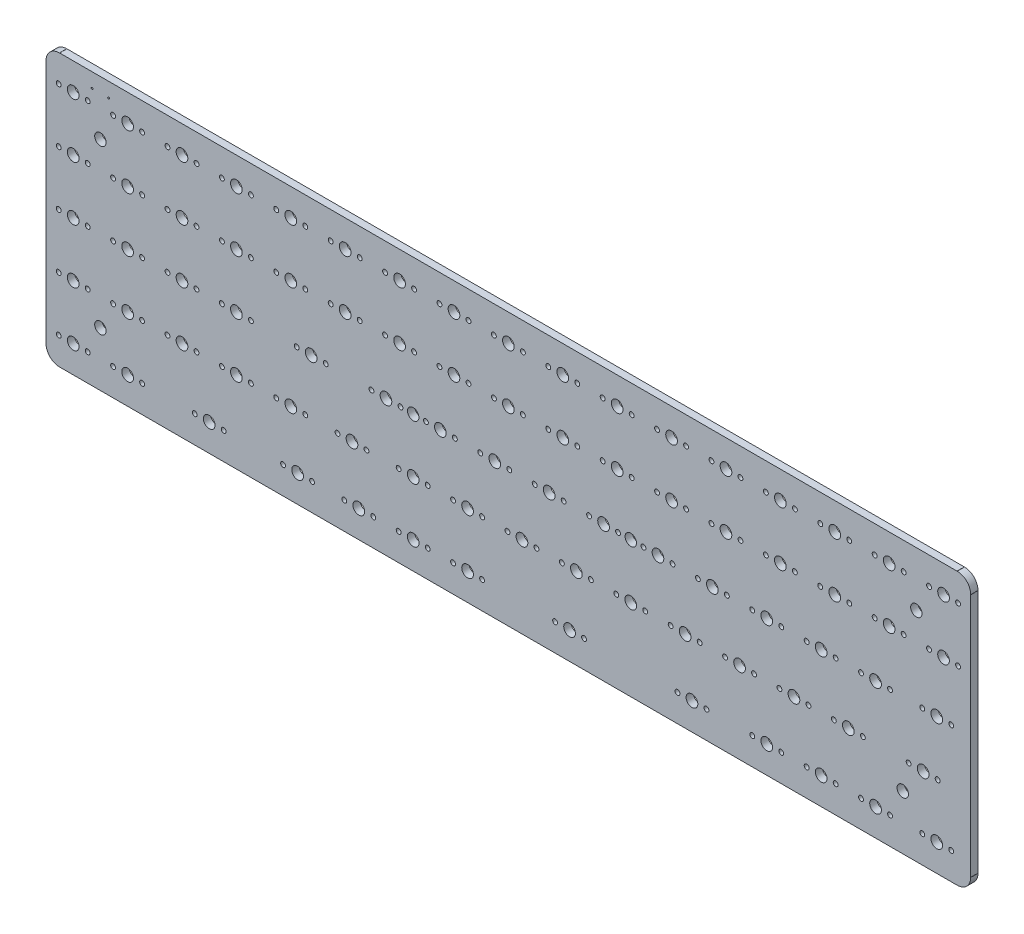
SolidWorks part; units mm, degrees
ref_plane "Front" through (0, 0, 0) normal (0, 0, 1) x (1, 0, 0)
ref_plane "Top" through (0, 0, 0) normal (0, 1, 0) x (1, 0, 0)
ref_plane "Right" through (0, 0, 0) normal (1, 0, 0) x (0, 0, -1)
sketch "Sketch2" plane through (0, 0, 0) normal (0, 0, 1) x (1, 0, 0)
  line L0 (314.325, -4.7625) -> (314.325, 80.9625)
  line L1 (309.5625, 85.725) -> (-4.7625, 85.725)
  line L2 (-9.525, 80.9625) -> (-9.525, -4.7625)
  line L3 (-4.7625, -9.525) -> (309.5625, -9.525)
  arc A0 (314.3631, 80.9625) -> (314.2869, 80.9625) centre (314.325, 80.9625) ccw
  arc A1 (314.2869, -4.7625) -> (314.3631, -4.7625) centre (314.325, -4.7625) ccw
  arc A2 (314.325, 80.9625) -> (309.5625, 85.725) centre (309.5624, 80.9624) ccw
  arc A3 (314.2869, 80.9625) -> (314.3631, 80.9625) centre (314.325, 80.9625) ccw
  arc A4 (309.5625, 85.7631) -> (309.5625, 85.6869) centre (309.5625, 85.725) ccw
  arc A5 (-4.7625, 85.7631) -> (-4.7625, 85.6869) centre (-4.7625, 85.725) ccw
  arc A6 (309.5625, 85.6869) -> (309.5625, 85.7631) centre (309.5625, 85.725) ccw
  arc A7 (-4.7625, 85.725) -> (-9.525, 80.9625) centre (-4.7624, 80.9624) ccw
  arc A8 (-4.7625, 85.6869) -> (-4.7625, 85.7631) centre (-4.7625, 85.725) ccw
  arc A9 (-9.5631, 80.9625) -> (-9.4869, 80.9625) centre (-9.525, 80.9625) ccw
  arc A10 (-9.5631, -4.7625) -> (-9.4869, -4.7625) centre (-9.525, -4.7625) ccw
  arc A11 (-9.4869, 80.9625) -> (-9.5631, 80.9625) centre (-9.525, 80.9625) ccw
  arc A12 (-9.525, -4.7625) -> (-4.7625, -9.525) centre (-4.7624, -4.7624) ccw
  arc A13 (-9.4869, -4.7625) -> (-9.5631, -4.7625) centre (-9.525, -4.7625) ccw
  arc A14 (-4.7625, -9.5631) -> (-4.7625, -9.4869) centre (-4.7625, -9.525) ccw
  arc A15 (309.5625, -9.5631) -> (309.5625, -9.4869) centre (309.5625, -9.525) ccw
  arc A16 (-4.7625, -9.4869) -> (-4.7625, -9.5631) centre (-4.7625, -9.525) ccw
  arc A17 (309.5625, -9.525) -> (314.325, -4.7625) centre (309.5624, -4.7624) ccw
  arc A18 (309.5625, -9.4869) -> (309.5625, -9.5631) centre (309.5625, -9.525) ccw
  arc A19 (314.3631, -4.7625) -> (314.2869, -4.7625) centre (314.325, -4.7625) ccw
  circle A20 centre (9.525, 66.675) radius 2
  circle A21 centre (9.525, 9.525) radius 2
  circle A22 centre (295.275, 66.675) radius 2
  circle A23 centre (290.5125, 9.525) radius 2
  circle A24 centre (119.0625, 38.1) radius 2
  circle A25 centre (195.2625, 38.1) radius 2
  circle A26 centre (304.8, 76.2) radius 2.0447
  circle A27 centre (299.72, 76.2) radius 0.8534
  circle A28 centre (309.88, 76.2) radius 0.8534
  circle A29 centre (285.75, 76.2) radius 2.0447
  circle A30 centre (280.67, 76.2) radius 0.8534
  circle A31 centre (290.83, 76.2) radius 0.8534
  circle A32 centre (266.7, 76.2) radius 2.0447
  circle A33 centre (261.62, 76.2) radius 0.8534
  circle A34 centre (271.78, 76.2) radius 0.8534
  circle A35 centre (247.65, 76.2) radius 2.0447
  circle A36 centre (242.57, 76.2) radius 0.8534
  circle A37 centre (252.73, 76.2) radius 0.8534
  circle A38 centre (228.6, 76.2) radius 2.0447
  circle A39 centre (223.52, 76.2) radius 0.8534
  circle A40 centre (233.68, 76.2) radius 0.8534
  circle A41 centre (209.55, 76.2) radius 2.0447
  circle A42 centre (204.47, 76.2) radius 0.8534
  circle A43 centre (214.63, 76.2) radius 0.8534
  circle A44 centre (190.5, 76.2) radius 2.0447
  circle A45 centre (185.42, 76.2) radius 0.8534
  circle A46 centre (195.58, 76.2) radius 0.8534
  circle A47 centre (171.45, 76.2) radius 2.0447
  circle A48 centre (166.37, 76.2) radius 0.8534
  circle A49 centre (176.53, 76.2) radius 0.8534
  circle A50 centre (152.4, 76.2) radius 2.0447
  circle A51 centre (147.32, 76.2) radius 0.8534
  circle A52 centre (157.48, 76.2) radius 0.8534
  circle A53 centre (133.35, 76.2) radius 2.0447
  circle A54 centre (128.27, 76.2) radius 0.8534
  circle A55 centre (138.43, 76.2) radius 0.8534
  circle A56 centre (114.3, 76.2) radius 2.0447
  circle A57 centre (109.22, 76.2) radius 0.8534
  circle A58 centre (119.38, 76.2) radius 0.8534
  circle A59 centre (95.25, 76.2) radius 2.0447
  circle A60 centre (90.17, 76.2) radius 0.8534
  circle A61 centre (100.33, 76.2) radius 0.8534
  circle A62 centre (76.2, 76.2) radius 2.0447
  circle A63 centre (71.12, 76.2) radius 0.8534
  circle A64 centre (81.28, 76.2) radius 0.8534
  circle A65 centre (57.15, 76.2) radius 2.0447
  circle A66 centre (52.07, 76.2) radius 0.8534
  circle A67 centre (62.23, 76.2) radius 0.8534
  circle A68 centre (38.1, 76.2) radius 2.0447
  circle A69 centre (33.02, 76.2) radius 0.8534
  circle A70 centre (43.18, 76.2) radius 0.8534
  circle A71 centre (19.05, 76.2) radius 2.0447
  circle A72 centre (13.97, 76.2) radius 0.8534
  circle A73 centre (24.13, 76.2) radius 0.8534
  circle A74 centre (0, 76.2) radius 2.0447
  circle A75 centre (-5.08, 76.2) radius 0.8534
  circle A76 centre (5.08, 76.2) radius 0.8534
  circle A77 centre (304.8, 57.15) radius 2.0447
  circle A78 centre (299.72, 57.15) radius 0.8534
  circle A79 centre (309.88, 57.15) radius 0.8534
  circle A80 centre (285.75, 57.15) radius 2.0447
  circle A81 centre (280.67, 57.15) radius 0.8534
  circle A82 centre (290.83, 57.15) radius 0.8534
  circle A83 centre (266.7, 57.15) radius 2.0447
  circle A84 centre (261.62, 57.15) radius 0.8534
  circle A85 centre (271.78, 57.15) radius 0.8534
  circle A86 centre (247.65, 57.15) radius 2.0447
  circle A87 centre (242.57, 57.15) radius 0.8534
  circle A88 centre (252.73, 57.15) radius 0.8534
  circle A89 centre (228.6, 57.15) radius 2.0447
  circle A90 centre (223.52, 57.15) radius 0.8534
  circle A91 centre (233.68, 57.15) radius 0.8534
  circle A92 centre (209.55, 57.15) radius 2.0447
  circle A93 centre (204.47, 57.15) radius 0.8534
  circle A94 centre (214.63, 57.15) radius 0.8534
  circle A95 centre (190.5, 57.15) radius 2.0447
  circle A96 centre (185.42, 57.15) radius 0.8534
  circle A97 centre (195.58, 57.15) radius 0.8534
  circle A98 centre (171.45, 57.15) radius 2.0447
  circle A99 centre (166.37, 57.15) radius 0.8534
  circle A100 centre (176.53, 57.15) radius 0.8534
  circle A101 centre (152.4, 57.15) radius 2.0447
  circle A102 centre (147.32, 57.15) radius 0.8534
  circle A103 centre (157.48, 57.15) radius 0.8534
  circle A104 centre (133.35, 57.15) radius 2.0447
  circle A105 centre (128.27, 57.15) radius 0.8534
  circle A106 centre (138.43, 57.15) radius 0.8534
  circle A107 centre (114.3, 57.15) radius 2.0447
  circle A108 centre (109.22, 57.15) radius 0.8534
  circle A109 centre (119.38, 57.15) radius 0.8534
  circle A110 centre (95.25, 57.15) radius 2.0447
  circle A111 centre (90.17, 57.15) radius 0.8534
  circle A112 centre (100.33, 57.15) radius 0.8534
  circle A113 centre (76.2, 57.15) radius 2.0447
  circle A114 centre (71.12, 57.15) radius 0.8534
  circle A115 centre (81.28, 57.15) radius 0.8534
  circle A116 centre (57.15, 57.15) radius 2.0447
  circle A117 centre (52.07, 57.15) radius 0.8534
  circle A118 centre (62.23, 57.15) radius 0.8534
  circle A119 centre (38.1, 57.15) radius 2.0447
  circle A120 centre (33.02, 57.15) radius 0.8534
  circle A121 centre (43.18, 57.15) radius 0.8534
  circle A122 centre (19.05, 57.15) radius 2.0447
  circle A123 centre (13.97, 57.15) radius 0.8534
  circle A124 centre (24.13, 57.15) radius 0.8534
  circle A125 centre (0, 57.15) radius 2.0447
  circle A126 centre (-5.08, 57.15) radius 0.8534
  circle A127 centre (5.08, 57.15) radius 0.8534
  circle A128 centre (302.4187, 38.1) radius 2.0447
  circle A129 centre (297.3388, 38.1) radius 0.8534
  circle A130 centre (307.4988, 38.1) radius 0.8534
  circle A131 centre (280.9875, 38.1) radius 2.0447
  circle A132 centre (275.9075, 38.1) radius 0.8534
  circle A133 centre (286.0675, 38.1) radius 0.8534
  circle A134 centre (261.9375, 38.1) radius 2.0447
  circle A135 centre (256.8575, 38.1) radius 0.8534
  circle A136 centre (267.0175, 38.1) radius 0.8534
  circle A137 centre (242.8875, 38.1) radius 2.0447
  circle A138 centre (237.8075, 38.1) radius 0.8534
  circle A139 centre (247.9675, 38.1) radius 0.8534
  circle A140 centre (223.8375, 38.1) radius 2.0447
  circle A141 centre (218.7575, 38.1) radius 0.8534
  circle A142 centre (228.9175, 38.1) radius 0.8534
  circle A143 centre (204.7875, 38.1) radius 2.0447
  circle A144 centre (199.7075, 38.1) radius 0.8534
  circle A145 centre (209.8675, 38.1) radius 0.8534
  circle A146 centre (185.7375, 38.1) radius 2.0447
  circle A147 centre (180.6575, 38.1) radius 0.8534
  circle A148 centre (190.8175, 38.1) radius 0.8534
  circle A149 centre (166.6875, 38.1) radius 2.0447
  circle A150 centre (161.6075, 38.1) radius 0.8534
  circle A151 centre (171.7675, 38.1) radius 0.8534
  circle A152 centre (147.6375, 38.1) radius 2.0447
  circle A153 centre (142.5575, 38.1) radius 0.8534
  circle A154 centre (152.7175, 38.1) radius 0.8534
  circle A155 centre (128.5875, 38.1) radius 2.0447
  circle A156 centre (123.5075, 38.1) radius 0.8534
  circle A157 centre (133.6675, 38.1) radius 0.8534
  circle A158 centre (109.5375, 38.1) radius 2.0447
  circle A159 centre (104.4575, 38.1) radius 0.8534
  circle A160 centre (114.6175, 38.1) radius 0.8534
  circle A161 centre (83.3438, 38.1) radius 2.0447
  circle A162 centre (78.2638, 38.1) radius 0.8534
  circle A163 centre (88.4237, 38.1) radius 0.8534
  circle A164 centre (57.15, 38.1) radius 2.0447
  circle A165 centre (52.07, 38.1) radius 0.8534
  circle A166 centre (62.23, 38.1) radius 0.8534
  circle A167 centre (38.1, 38.1) radius 2.0447
  circle A168 centre (33.02, 38.1) radius 0.8534
  circle A169 centre (43.18, 38.1) radius 0.8534
  circle A170 centre (19.05, 38.1) radius 2.0447
  circle A171 centre (13.97, 38.1) radius 0.8534
  circle A172 centre (24.13, 38.1) radius 0.8534
  circle A173 centre (0, 38.1) radius 2.0447
  circle A174 centre (-5.08, 38.1) radius 0.8534
  circle A175 centre (5.08, 38.1) radius 0.8534
  circle A176 centre (297.6563, 19.05) radius 2.0447
  circle A177 centre (292.5763, 19.05) radius 0.8534
  circle A178 centre (302.7363, 19.05) radius 0.8534
  circle A179 centre (271.4625, 19.05) radius 2.0447
  circle A180 centre (266.3825, 19.05) radius 0.8534
  circle A181 centre (276.5425, 19.05) radius 0.8534
  circle A182 centre (252.4125, 19.05) radius 2.0447
  circle A183 centre (247.3325, 19.05) radius 0.8534
  circle A184 centre (257.4925, 19.05) radius 0.8534
  circle A185 centre (233.3625, 19.05) radius 2.0447
  circle A186 centre (228.2825, 19.05) radius 0.8534
  circle A187 centre (238.4425, 19.05) radius 0.8534
  circle A188 centre (214.3125, 19.05) radius 2.0447
  circle A189 centre (209.2325, 19.05) radius 0.8534
  circle A190 centre (219.3925, 19.05) radius 0.8534
  circle A191 centre (195.2625, 19.05) radius 2.0447
  circle A192 centre (190.1825, 19.05) radius 0.8534
  circle A193 centre (200.3425, 19.05) radius 0.8534
  circle A194 centre (176.2125, 19.05) radius 2.0447
  circle A195 centre (171.1325, 19.05) radius 0.8534
  circle A196 centre (181.2925, 19.05) radius 0.8534
  circle A197 centre (157.1625, 19.05) radius 2.0447
  circle A198 centre (152.0825, 19.05) radius 0.8534
  circle A199 centre (162.2425, 19.05) radius 0.8534
  circle A200 centre (138.1125, 19.05) radius 2.0447
  circle A201 centre (133.0325, 19.05) radius 0.8534
  circle A202 centre (143.1925, 19.05) radius 0.8534
  circle A203 centre (119.0625, 19.05) radius 2.0447
  circle A204 centre (113.9825, 19.05) radius 0.8534
  circle A205 centre (124.1425, 19.05) radius 0.8534
  circle A206 centre (97.6313, 19.05) radius 2.0447
  circle A207 centre (92.5513, 19.05) radius 0.8534
  circle A208 centre (102.7113, 19.05) radius 0.8534
  circle A209 centre (76.2, 19.05) radius 2.0447
  circle A210 centre (71.12, 19.05) radius 0.8534
  circle A211 centre (81.28, 19.05) radius 0.8534
  circle A212 centre (57.15, 19.05) radius 2.0447
  circle A213 centre (52.07, 19.05) radius 0.8534
  circle A214 centre (62.23, 19.05) radius 0.8534
  circle A215 centre (38.1, 19.05) radius 2.0447
  circle A216 centre (33.02, 19.05) radius 0.8534
  circle A217 centre (43.18, 19.05) radius 0.8534
  circle A218 centre (19.05, 19.05) radius 2.0447
  circle A219 centre (13.97, 19.05) radius 0.8534
  circle A220 centre (24.13, 19.05) radius 0.8534
  circle A221 centre (0, 19.05) radius 2.0447
  circle A222 centre (-5.08, 19.05) radius 0.8534
  circle A223 centre (5.08, 19.05) radius 0.8534
  circle A224 centre (302.4187, 0) radius 2.0447
  circle A225 centre (297.3388, 0) radius 0.8534
  circle A226 centre (307.4988, 0) radius 0.8534
  circle A227 centre (280.9875, 0) radius 2.0447
  circle A228 centre (275.9075, 0) radius 0.8534
  circle A229 centre (286.0675, 0) radius 0.8534
  circle A230 centre (261.9375, 0) radius 2.0447
  circle A231 centre (256.8575, 0) radius 0.8534
  circle A232 centre (267.0175, 0) radius 0.8534
  circle A233 centre (242.8875, 0) radius 2.0447
  circle A234 centre (237.8075, 0) radius 0.8534
  circle A235 centre (247.9675, 0) radius 0.8534
  circle A236 centre (216.6938, 0) radius 2.0447
  circle A237 centre (211.6138, 0) radius 0.8534
  circle A238 centre (221.7738, 0) radius 0.8534
  circle A239 centre (173.8313, 0) radius 2.0447
  circle A240 centre (168.7512, 0) radius 0.8534
  circle A241 centre (178.9112, 0) radius 0.8534
  circle A242 centre (138.1125, 0) radius 2.0447
  circle A243 centre (133.0325, 0) radius 0.8534
  circle A244 centre (143.1925, 0) radius 0.8534
  circle A245 centre (119.0625, 0) radius 2.0447
  circle A246 centre (113.9825, 0) radius 0.8534
  circle A247 centre (124.1425, 0) radius 0.8534
  circle A248 centre (100.0125, 0) radius 2.0447
  circle A249 centre (94.9325, 0) radius 0.8534
  circle A250 centre (105.0925, 0) radius 0.8534
  circle A251 centre (78.5812, 0) radius 2.0447
  circle A252 centre (73.5012, 0) radius 0.8534
  circle A253 centre (83.6613, 0) radius 0.8534
  circle A254 centre (47.625, 0) radius 2.0447
  circle A255 centre (42.545, 0) radius 0.8534
  circle A256 centre (52.705, 0) radius 0.8534
  circle A257 centre (19.05, 0) radius 2.0447
  circle A258 centre (13.97, 0) radius 0.8534
  circle A259 centre (24.13, 0) radius 0.8534
  circle A260 centre (0, 0) radius 2.0447
  circle A261 centre (-5.08, 0) radius 0.8534
  circle A262 centre (5.08, 0) radius 0.8534
  circle A263 centre (12.415, 80.6463) radius 0.325
  circle A264 centre (6.635, 80.6463) radius 0.325
extrude "Boss-Extrude3" add sketch "Sketch2" along normal mid plane 2.54 contours A19 L0 A3 A0 A2 A6 A4 L1 A8 A5 A7 A11 A9 L2 A13 A10 A12 A16 A14 L3 A18 A15 A17 A1 A264 A263 A262 A261 A260 A259 A258 A257 A256 A255 A254 A253 A252 region at (311.9111, -2.3486, 0)
ref_plane "Plane1" through (0, 38.1, 0) normal (0, 1, 0) x (1, 0, 0)
ref_plane "Plane2" through (152.4, 0, 0) normal (1, 0, 0) x (0, 0, -1)
